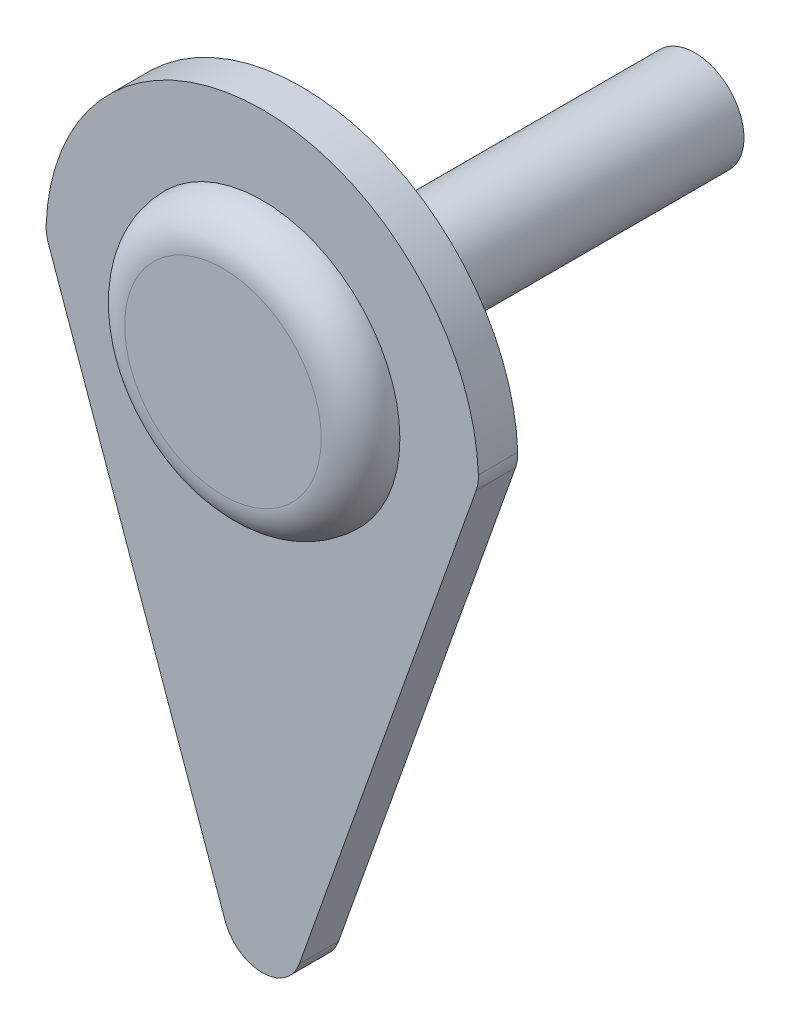
SolidWorks part; units mm, degrees
ref_plane "Front Plane" through (0, 0, 0) normal (0, 0, 1) x (1, 0, 0)
ref_plane "Top Plane" through (0, 0, 0) normal (0, 1, 0) x (1, 0, 0)
ref_plane "Right Plane" through (0, 0, 0) normal (1, 0, 0) x (0, 0, -1)
sketch "Szkic1" plane through (0, 0, 0) normal (0, 0, 1) x (1, 0, 0)
  line L0 (0.9424, 2.6559) -> (5.4394, 15.3294)
  line L1 (0, 0) -> (0, 21) construction
  line L2 (-0.9424, 2.6559) -> (-5.4394, 15.3294)
  arc A0 (5.4964, 15.7002) -> (-5.4964, 15.7002) centre (0, 15.5) ccw
  arc A1 (5.4394, 15.3294) -> (5.4964, 15.7002) centre (4.497, 15.6638) ccw
  arc A2 (0.9424, 2.6559) -> (-0.9424, 2.6559) centre (0, 2.9903) cw
  arc A3 (-5.4394, 15.3294) -> (-5.4964, 15.7002) centre (-4.497, 15.6638) cw
  point P9 (5.5, 15.5)
  point P15 (-5.5, 15.5)
  dimension "D3" = 5.5
  dimension "D5" = 1
  dimension "D1" = 21
  dimension "D2" = 11
  dimension "D4" = 15.5
extrude "Dodanie-wyciągnięcie1" add sketch "Szkic1" along normal blind 1
sketch "Szkic2" plane through (0, 0, 1) normal (0, 0, 1) x (1, 0, 0)
  circle A0 centre (0, 15.5) radius 3.5
  arc A1 (5.4964, 15.7002) -> (-5.4964, 15.7002) centre (0, 15.5) ccw construction
  dimension "D1" = 7
extrude "Dodanie-wyciągnięcie2" add sketch "Szkic2" along normal blind 1 contours A0
sketch "Szkic3" plane through (0, 0, 0) normal (0, 0, -1) x (-1, 0, 0)
  circle A0 centre (0, 15.5) radius 1.25
  arc A1 (5.4964, 15.7002) -> (-5.4964, 15.7002) centre (0, 15.5) ccw construction
  dimension "D1" = 2.5
extrude "Dodanie-wyciągnięcie3" add sketch "Szkic3" along normal blind 10
fillet "Zaokrąglenie1" radius 1 1 edges at (3.5, 15.5, 2)
